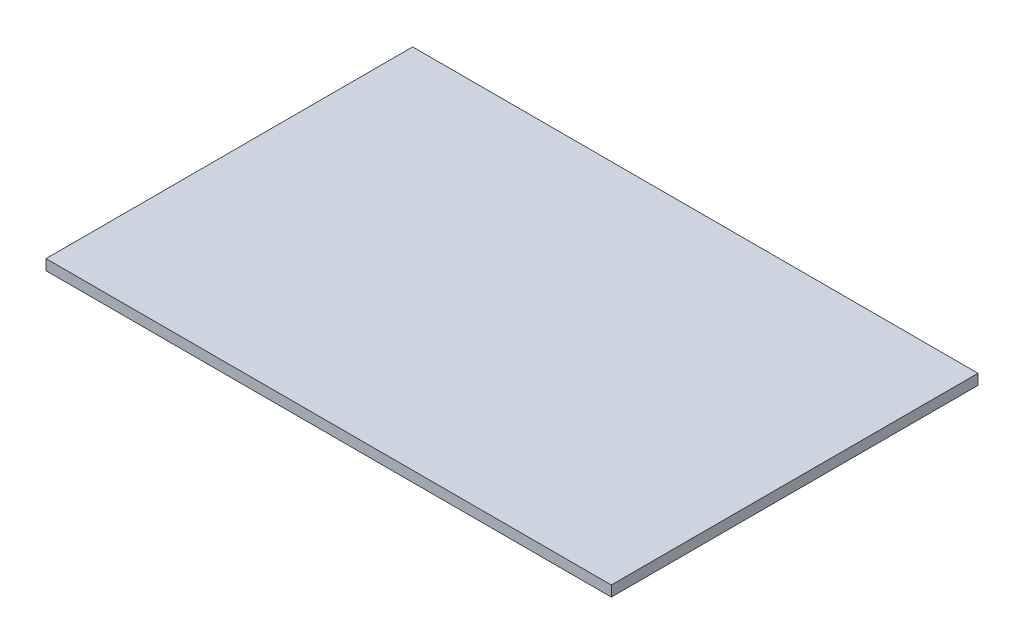
SolidWorks part; units mm, degrees
material "Cedar"
ref_plane "Front Plane" through (0, 0, 0) normal (0, 0, 1) x (1, 0, 0)
ref_plane "Top Plane" through (0, 0, 0) normal (0, 1, 0) x (1, 0, 0)
ref_plane "Right Plane" through (0, 0, 0) normal (1, 0, 0) x (0, 0, -1)
sketch "Sketch1" plane through (0, 0, 0) normal (0, 1, 0) x (1, 0, 0)
  line L1 (-469.9, -304.8) -> (469.9, -304.8)
  line L2 (-469.9, -304.8) -> (-469.9, 304.8)
  line L3 (-469.9, 304.8) -> (469.9, 304.8)
  line L4 (469.9, -304.8) -> (469.9, 304.8)
  line L5 (-469.9, -304.8) -> (469.9, 304.8) construction
  line L6 (-469.9, 304.8) -> (469.9, -304.8) construction
  point P0 (0, 0)
  dimension "D1" = 939.8
  dimension "D2" = 609.6
extrude "Boss-Extrude1" add sketch "Sketch1" along normal blind 17.4752
